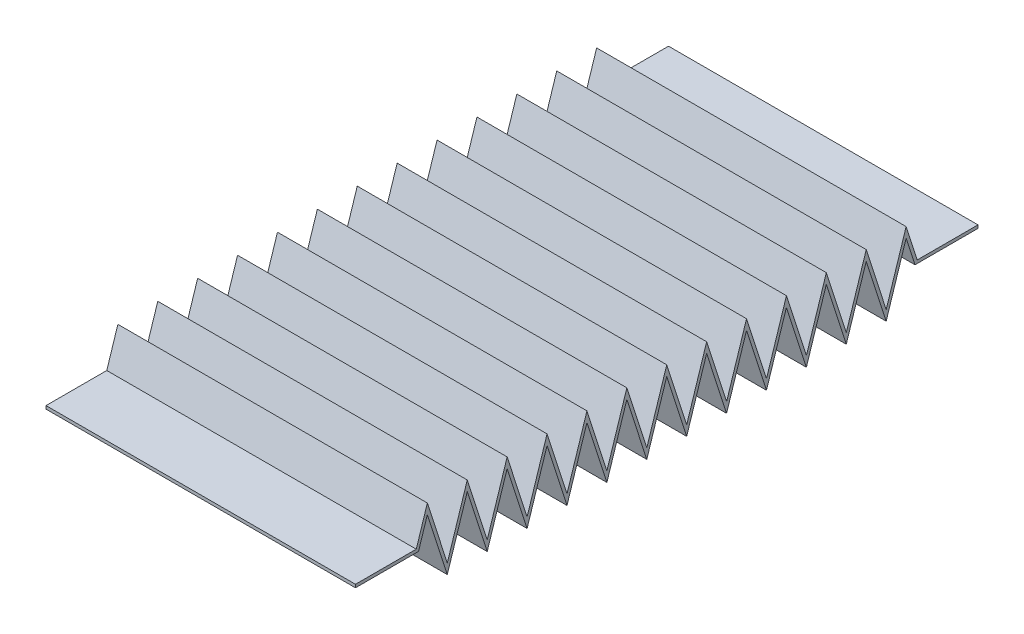
SolidWorks part; units mm, degrees
ref_plane "Front Plane" through (0, 0, 0) normal (0, 0, 1) x (1, 0, 0)
ref_plane "Top Plane" through (0, 0, 0) normal (0, 1, 0) x (1, 0, 0)
ref_plane "Right Plane" through (0, 0, 0) normal (1, 0, 0) x (0, 0, -1)
sketch "Sketch2" plane through (0, 0, 0) normal (0, 0, 1) x (1, 0, 0)
  line L1 (-27.5, 10) -> (27.5, 10)
  line L2 (-27.5, 10) -> (-27.5, 0)
  line L3 (-27.5, 0) -> (27.5, 0)
  line L4 (27.5, 10) -> (27.5, 0)
  point P4 (0, 0)
  dimension "D1" = 10
  dimension "D2" = 55
sketch "Sketch3" plane through (0, 0, 0) normal (1, 0, 0) x (0, 0, -1)
  line L0 (0, 10) -> (100.5739, 10) construction
  line L1 (0, 0) -> (100.5739, 0) construction
  line L3 (10, 5) -> (11.6115, 10)
  line L4 (11.6115, 10) -> (14.8344, 0)
  line L5 (14.8344, 0) -> (18.0574, 10)
  line L6 (18.0574, 10) -> (21.2803, 0)
  line L7 (21.2803, 0) -> (24.5033, 10)
  line L8 (24.5033, 10) -> (27.7263, 0)
  line L9 (27.7263, 0) -> (30.9492, 10)
  line L10 (30.9492, 10) -> (34.1722, 0)
  line L11 (34.1722, 0) -> (37.3951, 10)
  line L12 (37.3951, 10) -> (40.6181, 0)
  line L13 (40.6181, 0) -> (43.841, 10)
  line L14 (43.841, 10) -> (47.064, 0)
  line L15 (47.064, 0) -> (50.287, 10)
  line L16 (50.287, 10) -> (53.5099, 0)
  line L17 (53.5099, 0) -> (56.7329, 10)
  line L18 (56.7329, 10) -> (59.9558, 0)
  line L19 (0, 10) -> (0, 0) construction
  line L20 (59.9558, 0) -> (63.1788, 10)
  line L21 (63.1788, 10) -> (66.4017, 0)
  line L22 (66.4017, 0) -> (69.6247, 10)
  line L23 (69.6247, 10) -> (72.8476, 0)
  line L24 (72.8476, 0) -> (76.0706, 10)
  line L25 (76.0706, 10) -> (79.2936, 0)
  line L26 (79.2936, 0) -> (82.5165, 10)
  line L27 (82.5165, 10) -> (85.7395, 0)
  line L28 (85.7395, 0) -> (88.9624, 10)
  line L29 (88.9624, 10) -> (90.5739, 5)
  line L30 (100.5739, 10) -> (100.5739, 0) construction
  line L31 (10, 5) -> (0, 5)
  line L32 (90.5739, 5) -> (100.5739, 5)
  line L34 (100.5739, 22.75) -> (100.5739, 4.75) construction
  dimension "D2" = 10
  dimension "D1" = 10
  dimension "D3" = 10
extrude "Extrude-Thin1" add sketch "Sketch3" against normal mid plane 50 thin thin type mid plane wall 0.5
